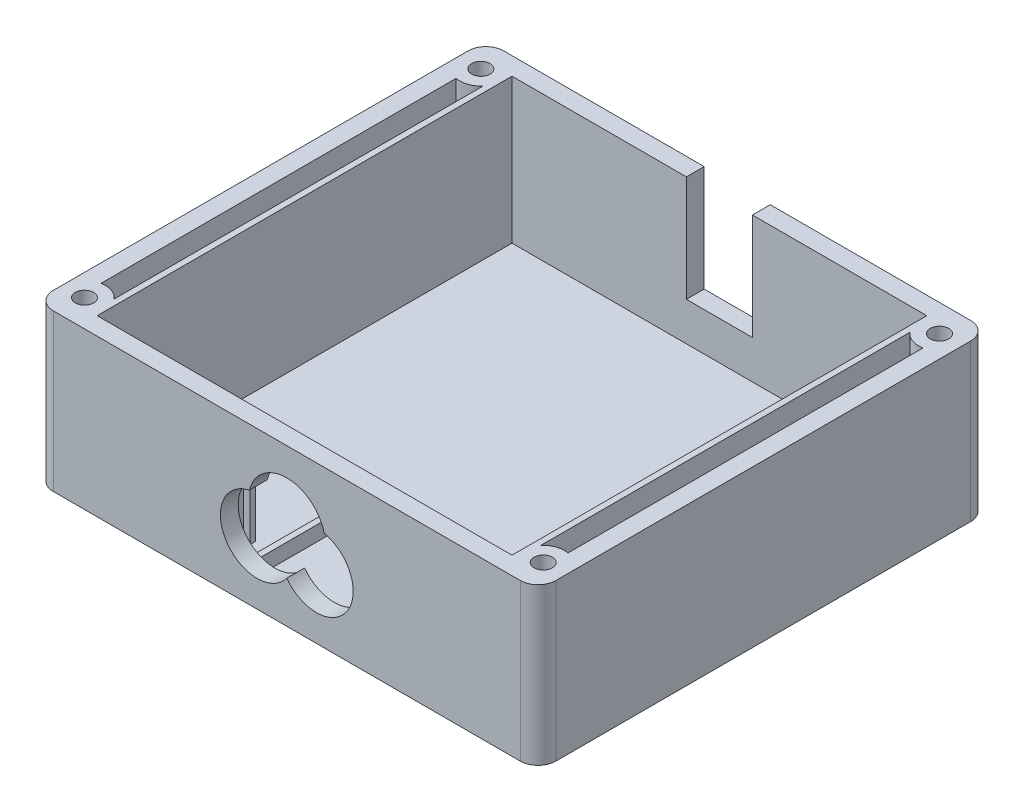
SolidWorks part; units mm, degrees
ref_plane "Front Plane" through (0, 0, 0) normal (0, 0, 1) x (1, 0, 0)
ref_plane "Top Plane" through (0, 0, 0) normal (0, 1, 0) x (1, 0, 0)
ref_plane "Right Plane" through (0, 0, 0) normal (1, 0, 0) x (0, 0, -1)
sketch "Sketch2" plane through (0, 0, 0) normal (0, 1, 0) x (1, 0, 0)
  line L1 (-35, 35) -> (35, 35)
  line L2 (-35, 35) -> (-35, -35)
  line L3 (-35, -35) -> (35, -35)
  line L4 (35, 35) -> (35, -35)
  line L5 (-35, 35) -> (35, -35) construction
  line L6 (-35, -35) -> (35, 35) construction
  point P0 (0, 0)
  dimension "D1" = 70
extrude "Boss-Extrude1" add sketch "Sketch2" along normal blind 2
sketch "Sketch3" plane through (0, 2, 0) normal (0, 1, 0) x (1, 0, 0)
  line L0 (-7.8, -28.6445) -> (7.8, -28.6445) construction
  line L1 (-35, -35) -> (35, -35) construction
  line L3 (14.15, -31.2) -> (14.15, -35)
  line L4 (14.15, -35) -> (15.15, -35)
  line L5 (15.15, -30.2) -> (15.15, -35)
  line L6 (-15.15, -30.2) -> (-13.05, -30.2)
  line L8 (-14.15, -31.2) -> (-14.15, -35)
  line L9 (-14.15, -35) -> (-15.15, -35)
  line L10 (-15.15, -30.2) -> (-15.15, -35)
  line L11 (-13.05, -30.2) -> (-13.05, -31.2)
  line L12 (-13.05, -31.2) -> (-14.15, -31.2)
  line L13 (15.15, -30.2) -> (13.05, -30.2)
  line L14 (13.05, -30.2) -> (13.05, -31.2)
  line L15 (13.05, -31.2) -> (14.15, -31.2)
  line L16 (-14.15, -35.7358) -> (14.15, -35.7358) construction
  line L18 (7.8, -20) -> (8.8, -20)
  line L19 (7.8, -20) -> (7.8, -35)
  line L20 (7.8, -35) -> (8.8, -35)
  line L21 (8.8, -20) -> (8.8, -35)
  line L22 (-7.8, -20) -> (-8.8, -20)
  line L23 (-7.8, -20) -> (-7.8, -35)
  line L24 (-7.8, -35) -> (-8.8, -35)
  line L25 (-8.8, -20) -> (-8.8, -35)
  point P24 (0, -35.7358)
  point P27 (0, -28.6445)
  line M20 (-35, -35) -> (35, -35)
  dimension "D1" = 28.3
  dimension "D2" = 1
  dimension "D3" = 15.6
  dimension "D4" = 1.1
  dimension "D5" = 1
  dimension "D6" = 1
  dimension "D7" = 4.8
  dimension "D8" = 30.3
  dimension "D9" = 15
  dimension "D10" = 1
extrude "Boss-Extrude2" add sketch "Sketch3" along normal blind 18 contours L14 L15 L3 L5 L13 M20 | L12 L11 L6 L10 L8 M20 region at (14.4542, 2, 32.2458) region at (-14.4542, 2, 32.2458)
extrude "Boss-Extrude3" add sketch "Sketch3<3>" along normal blind 2.5 contours L22 L25 L23 M20 | L21 L18 L19 M20 region at (-8.3, 2, 27.5) region at (8.3, 2, 27.5)
sketch "Sketch3<3>" plane through (0, 2, 0) normal (0, 1, 0) x (1, 0, 0) same geometry as "Sketch3"
sketch "Sketch4" plane through (0, 0, 0) normal (0, 1, 0) x (1, 0, 0)
  line L1 (-36, 38) -> (36, 38)
  line L2 (-36, 38) -> (-36, -38)
  line L3 (-36, -38) -> (36, -38)
  line L4 (36, 38) -> (36, -38)
  line L5 (-36, 38) -> (36, -38) construction
  line L6 (-36, -38) -> (36, 38) construction
  line L8 (-35, 35) -> (35, 35)
  line L9 (-35, 35) -> (-35, -35)
  line L10 (-35, -35) -> (35, -35)
  line L11 (35, 35) -> (35, -35)
  point P0 (0, 0)
  dimension "D1" = 1
  dimension "D2" = 3
extrude "Boss-Extrude4" add sketch "Sketch4" along normal blind 26.4
sketch "Sketch12" plane through (0, 0, 0) normal (0, 1, 0) x (1, 0, 0)
  line L0 (36, -38) -> (36, 38) construction
  line L1 (41.4, -35) -> (41.4, -31.8823) construction
  line L2 (41.4, -31.8823) -> (38.7, -30.3235) construction
  line L3 (38.7, -30.3235) -> (36, -31.8823) construction
  line L4 (36, -31.8823) -> (36, -35) construction
  line L5 (36, -35) -> (38.7, -36.5588) construction
  line L6 (38.7, -36.5588) -> (41.4, -35) construction
  line L7 (36, -38) -> (42.4, -38)
  line L8 (42.4, -38) -> (42.4, 38)
  line L9 (42.4, 38) -> (36, 38)
  line L10 (39.4, 29.9609) -> (39.4, -29.9609)
  line L11 (36, -38) -> (36, -35.746)
  line L12 (36, 35) -> (35, 35) construction
  line L13 (35, -35) -> (36, -35) construction
  line L14 (38.7, 30.3235) -> (41.4, 31.8823) construction
  line L15 (41.4, 31.8823) -> (41.4, 35) construction
  line L16 (41.4, 35) -> (38.7, 36.5588) construction
  line L17 (38.7, 36.5588) -> (36, 35) construction
  line L18 (36, 35) -> (36, 31.8823) construction
  line L19 (36, 31.8823) -> (38.7, 30.3235) construction
  line L20 (36, 38) -> (36, 35.746)
  line L21 (0, -35) -> (0, 35) construction
  line L22 (-35, -35) -> (35, -35) construction
  line L23 (35, 35) -> (-35, 35) construction
  line L24 (-36, 31.8823) -> (-38.7, 30.3235) construction
  line L25 (-36, 35) -> (-36, 31.8823) construction
  line L26 (-38.7, 36.5588) -> (-36, 35) construction
  line L27 (-41.4, 35) -> (-38.7, 36.5588) construction
  line L28 (-41.4, 31.8823) -> (-41.4, 35) construction
  line L29 (-38.7, 30.3235) -> (-41.4, 31.8823) construction
  line L30 (-35, -35) -> (-36, -35) construction
  line L31 (-36, 35) -> (-35, 35) construction
  line L32 (-38.7, -36.5588) -> (-41.4, -35) construction
  line L33 (-36, -35) -> (-38.7, -36.5588) construction
  line L34 (-36, -31.8823) -> (-36, -35) construction
  line L35 (-38.7, -30.3235) -> (-36, -31.8823) construction
  line L36 (-41.4, -31.8823) -> (-38.7, -30.3235) construction
  line L37 (-41.4, -35) -> (-41.4, -31.8823) construction
  line L38 (-36, 38) -> (-36, 35.746)
  line L39 (-36, -38) -> (-36, -35.746)
  line L40 (-39.4, 29.9609) -> (-39.4, -29.9609)
  line L41 (-42.4, 38) -> (-36, 38)
  line L42 (-42.4, -38) -> (-42.4, 38)
  line L43 (-36, -38) -> (-42.4, -38)
  circle A0 centre (38.7, -33.4412) radius 2.7 construction
  circle A1 centre (38.7, -33.4412) radius 1.55
  arc A2 (39.4, -29.9609) -> (36, -35.746) centre (38.7, -33.4412) ccw
  circle A3 centre (38.7, -33.4412) radius 3.55 construction
  circle A4 centre (38.7, 33.4412) radius 2.7 construction
  circle A5 centre (38.7, 33.4412) radius 1.55
  arc A6 (36, 35.746) -> (39.4, 29.9609) centre (38.7, 33.4412) ccw
  circle A7 centre (38.7, 33.4412) radius 3.55 construction
  circle A8 centre (-38.7, 33.4412) radius 2.7 construction
  circle A9 centre (-38.7, -33.4412) radius 2.7 construction
  arc A10 (-36, 35.746) -> (-39.4, 29.9609) centre (-38.7, 33.4412) cw
  circle A11 centre (-38.7, 33.4412) radius 1.55
  arc A12 (-39.4, -29.9609) -> (-36, -35.746) centre (-38.7, -33.4412) cw
  circle A13 centre (-38.7, -33.4412) radius 1.55
  dimension "D2" = 3.1
  dimension "D4" = 2
  dimension "D7" = 3.1
  dimension "D1" = 5.4
  dimension "D3" = 1
  dimension "D5" = 3
  dimension "D6" = 5.4
  dimension "D8" = 2
extrude "Boss-Extrude10" add sketch "Sketch12" along normal up to surface (26.4 mm away) up to face at (0, 26.4, 0)
sketch "Sketch13" plane through (0, 0, 0) normal (0, 1, 0) x (1, 0, 0)
  line L0 (39.4, 29.9609) -> (39.4, -29.9609) construction
  line L1 (36, -31.1363) -> (36, 31.1363) construction
  line L2 (39.4, 29.9609) -> (39.4, -29.9609)
  line L3 (36, -31.1363) -> (36, 31.1363)
  line L4 (-39.4, -29.9609) -> (-39.4, 29.9609) construction
  line L5 (-36, 31.1363) -> (-36, -31.1363) construction
  line L6 (-39.4, -29.9609) -> (-39.4, 29.9609)
  line L7 (-36, 31.1363) -> (-36, -31.1363)
  arc A0 (39.4, -29.9609) -> (36, -31.1363) centre (38.7, -33.4412) ccw construction
  arc A1 (36, 31.1363) -> (39.4, 29.9609) centre (38.7, 33.4412) ccw construction
  arc A2 (39.4, -29.9609) -> (36, -31.1363) centre (38.7, -33.4412) ccw
  arc A3 (36, 31.1363) -> (39.4, 29.9609) centre (38.7, 33.4412) ccw
  arc A4 (-36, -31.1363) -> (-39.4, -29.9609) centre (-38.7, -33.4412) ccw construction
  arc A5 (-39.4, 29.9609) -> (-36, 31.1363) centre (-38.7, 33.4412) ccw construction
  arc A6 (-36, -31.1363) -> (-39.4, -29.9609) centre (-38.7, -33.4412) ccw
  arc A7 (-39.4, 29.9609) -> (-36, 31.1363) centre (-38.7, 33.4412) ccw
extrude "Boss-Extrude11" add sketch "Sketch13" along normal blind 5
sketch "Sketch1" plane through (0, 0, 38) normal (0, 0, 1) x (1, 0, 0)
  line L0 (-5, 10.7) -> (5, 10.7) construction
  line L1 (0, 15.2) -> (0, 10.7) construction
  line L2 (-42.4, 0) -> (42.4, 0) construction
  circle A0 centre (-5, 10.7) radius 1.18
  circle A1 centre (5, 10.7) radius 1.18
  circle A2 centre (0, 15.2) radius 1.6
  arc A3 (-0.8006, 10.7718) -> (0.8006, 10.7718) centre (0, 15.2) ccw
  arc A4 (0.8006, 10.7718) -> (4.4878, 14.8686) centre (5, 10.7) ccw
  arc A5 (-4.4878, 14.8686) -> (-0.8006, 10.7718) centre (-5, 10.7) ccw
  arc A6 (4.4878, 14.8686) -> (-4.4878, 14.8686) centre (0, 15.2) ccw
  arc A7 (0, 7.0339) -> (6.31, 16.76) centre (5, 10.7) ccw
  arc A8 (6.31, 16.76) -> (-6.31, 16.76) centre (0, 15.2) ccw
  arc A9 (-6.31, 16.76) -> (0, 7.0339) centre (-5, 10.7) ccw
  arc A10 (0, 7.0339) -> (0, 7.0339) centre (0, 7.0339) ccw
  point P4 (0, 0)
  dimension "D1" = 10
  dimension "D3" = 3.2
  dimension "D4" = 2.36
  dimension "D5" = 8.4
  dimension "D6" = 9
  dimension "D9" = 10.7
  dimension "D2" = 4.5
  dimension "D8" = 4.5
  dimension "D7" = 2
extrude "Cut-Extrude1" cut sketch "Sketch1" against normal blind 25 contours A8 A9 A7 A6 A4 A3 A5 | A4 A6 A5 A3 A0 A1 A2 | A2 | A1 | A0 region at (-5, 10.7, 38) region at (5, 10.7, 38) region at (0, 15.2, 38) region at (0, 12.2281, 38) region at (-9.9643, 7.4793, 38)
fillet "Fillet1" radius 3 4 edges at (-42.4, 13.2, 38) (42.4, 13.2, 38) (-42.4, 13.2, -38) (42.4, 13.2, -38)
sketch "Sketch14" plane through (0, 0, 0) normal (0, -1, 0) x (1, 0, 0)
  line L1 (-41.425, 31.8679) -> (-38.7, 30.2946)
  line L2 (-38.7, 30.2946) -> (-35.975, 31.8679)
  line L3 (-35.975, 31.8679) -> (-35.975, 35.0144)
  line L4 (-35.975, 35.0144) -> (-38.7, 36.5877)
  line L5 (-38.7, 36.5877) -> (-41.425, 35.0144)
  line L6 (-41.425, 35.0144) -> (-41.425, 31.8679)
  line L7 (41.425, 31.8679) -> (41.425, 35.0144)
  line L8 (41.425, 35.0144) -> (38.7, 36.5877)
  line L9 (38.7, 36.5877) -> (35.975, 35.0144)
  line L10 (35.975, 35.0144) -> (35.975, 31.8679)
  line L11 (35.975, 31.8679) -> (38.7, 30.2946)
  line L12 (38.7, 30.2946) -> (41.425, 31.8679)
  line L13 (41.425, -35.0144) -> (41.425, -31.8679)
  line L14 (41.425, -31.8679) -> (38.7, -30.2946)
  line L15 (38.7, -30.2946) -> (35.975, -31.8679)
  line L16 (35.975, -31.8679) -> (35.975, -35.0144)
  line L17 (35.975, -35.0144) -> (38.7, -36.5877)
  line L18 (38.7, -36.5877) -> (41.425, -35.0144)
  line L19 (-35.975, -35.0144) -> (-35.975, -31.8679)
  line L20 (-35.975, -31.8679) -> (-38.7, -30.2946)
  line L21 (-38.7, -30.2946) -> (-41.425, -31.8679)
  line L22 (-41.425, -31.8679) -> (-41.425, -35.0144)
  line L23 (-41.425, -35.0144) -> (-38.7, -36.5877)
  line L24 (-38.7, -36.5877) -> (-35.975, -35.0144)
  circle A0 centre (-38.7, 33.4412) radius 2.725 construction
  circle A1 centre (38.7, 33.4412) radius 2.725 construction
  circle A2 centre (38.7, -33.4412) radius 2.725 construction
  circle A3 centre (-38.7, -33.4412) radius 2.725 construction
  dimension "D1" = 5.45
extrude "Cut-Extrude4" cut sketch "Sketch14" against normal blind 2.7
sketch "Sketch15" plane through (0, 0, -38) normal (0, 0, -1) x (-1, 0, 0)
  line L0 (0, 0) -> (0, 14) construction
  line L1 (-39.4, 26.4) -> (39.4, 26.4) construction
  line L3 (-5.575, 14) -> (-5.575, 26.4)
  line L4 (-5.575, 26.4) -> (5.575, 26.4)
  line L5 (5.575, 14) -> (5.575, 26.4)
  line L6 (0, 8.5) -> (0, 0) construction
  line L8 (5.575, 14) -> (5.575, 8.5)
  line L9 (5.575, 8.5) -> (-5.575, 8.5)
  line L10 (-5.575, 14) -> (-5.575, 8.5)
  dimension "D1" = 11.15
  dimension "D2" = 14
  dimension "D4" = 5.5
extrude "Cut-Extrude5" cut sketch "Sketch15" against normal blind 10
